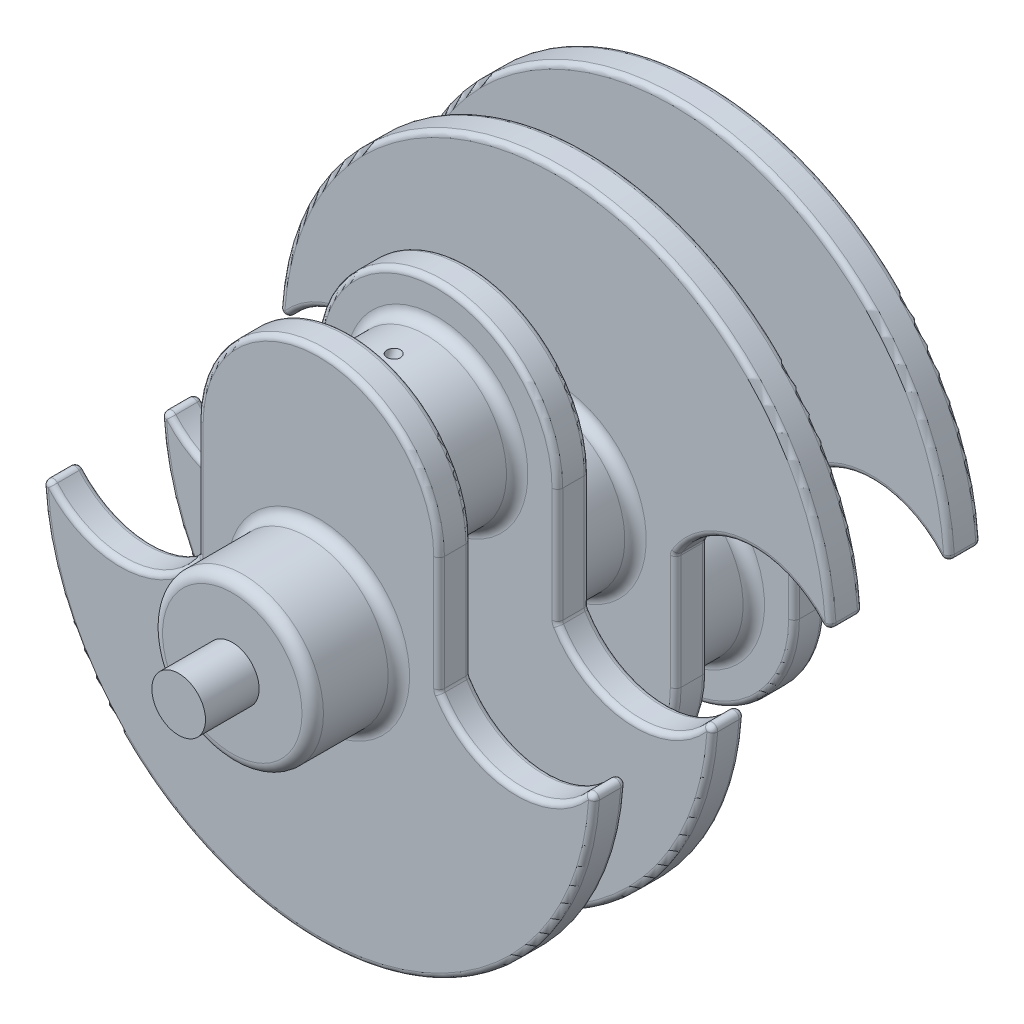
SolidWorks part; units mm, degrees
material "AISI 4340 Steel, normalized"
ref_plane "Front Plane" through (0, 0, 0) normal (0, 0, 1) x (1, 0, 0)
ref_plane "Top Plane" through (0, 0, 0) normal (0, 1, 0) x (1, 0, 0)
ref_plane "Right Plane" through (0, 0, 0) normal (1, 0, 0) x (0, 0, -1)
sketch "Sketch1" plane through (0, 0, 0) normal (0, 0, 1) x (1, 0, 0)
  circle A0 centre (0, 0) radius 30
  dimension "D1" = 30
extrude "Boss-Extrude1" add sketch "Sketch1" along normal blind 32.13
sketch "Sketch8" plane through (0, 0, 0) normal (0, 0, -1) x (-1, 0, 0)
  line L0 (-45, 43.2) -> (-45, 0)
  line L1 (45, 43.2) -> (45, 0)
  line L2 (-45, 0) -> (-89.1072, 0) construction
  arc A0 (45, 43.2) -> (-45, 43.2) centre (0, 43.2) ccw
  arc A5 (-103, 0) -> (103, 0) centre (0, 0) ccw
  arc A6 (-45, 0) -> (-103, 0) centre (-74, 16.8638) cw
  arc A7 (45, 0) -> (103, 0) centre (74, 16.8638) ccw
  dimension "D1" = 45
  dimension "D2" = 103
  dimension "D3" = 43.2
  dimension "D4" = 0
  dimension "D5" = 180
  dimension "D6" = 0
extrude "Boss-Extrude5" add sketch "Sketch8" along normal blind 12
sketch "Sketch2" plane through (0, 0, 32.13) normal (0, 0, 1) x (1, 0, 0)
  circle A0 centre (0, 0) radius 10
  dimension "D1" = 10
extrude "Boss-Extrude2" add sketch "Sketch2" along normal blind 20
sketch "Sketch9" plane through (0, 0, -12) normal (0, 0, -1) x (-1, 0, 0)
  circle A0 centre (0, 43.2) radius 30
  dimension "D2" = 30
  dimension "D1" = 43.2
extrude "Boss-Extrude6" add sketch "Sketch9" along normal blind 32.13
ref_plane "Plane4" through (0, 0, -88.26) normal (0, 0, -1) x (-1, 0, 0)
sketch "Sketch10" plane through (0, 0, -44.13) normal (0, 0, -1) x (-1, 0, 0)
  line L0 (-45, -43.2) -> (-45, 0)
  line L1 (45, -43.2) -> (45, 0)
  line L2 (45, 0) -> (85.967, 0) construction
  arc A0 (-45, -43.2) -> (45, -43.2) centre (0, -43.2) ccw
  arc A1 (-45, 0) -> (-103, 0) centre (-74, -16.8638) ccw
  arc A2 (45, 0) -> (103, 0) centre (74, -16.8638) cw
  arc A3 (-103, 0) -> (103, 0) centre (0, 0) cw
  dimension "D1" = 45
  dimension "D4" = 0
  dimension "D5" = 180
  dimension "D6" = 0
  dimension "D3" = 103
  dimension "D2" = 43.2
extrude "Boss-Extrude7" add sketch "Sketch10" along normal blind 12 from surface starting at plane "Plane4"
ref_plane "Plane3" through (0, 0, -132.39) normal (0, 0, -1) x (-1, 0, 0)
sketch "Sketch12" plane through (0, 0, -132.39) normal (0, 0, -1) x (-1, 0, 0)
  line L2 (45, -43.2) -> (45, 0)
  line L3 (45, -43.2) -> (45, 0)
  line L4 (-45, 0) -> (-45, -43.2)
  line L5 (-45, 0) -> (-45, -43.2)
  arc A12 (-45, -43.2) -> (45, -43.2) centre (0, -43.2) ccw
  arc A13 (103, 0) -> (45, 0) centre (74, -16.8638) ccw
  arc A14 (103, 0) -> (-103, 0) centre (0, 0) ccw
  arc A15 (-45, 0) -> (-103, 0) centre (-74, -16.8638) ccw
  arc A16 (-45, -43.2) -> (45, -43.2) centre (0, -43.2) ccw
  arc A17 (103, 0) -> (45, 0) centre (74, -16.8638) ccw
  arc A18 (103, 0) -> (-103, 0) centre (0, 0) ccw
  arc A19 (-45, 0) -> (-103, 0) centre (-74, -16.8638) ccw
  dimension "D1" = 0
extrude "Boss-Extrude8" add sketch "Sketch12" along normal blind 12
sketch "Sketch14" plane through (0, 0, -100.26) normal (0, 0, -1) x (-1, 0, 0)
  circle A0 centre (0, -43.2) radius 30
  dimension "D2" = 30
  dimension "D1" = 43.2
extrude "Boss-Extrude9" add sketch "Sketch14" along normal up to next
sketch "Sketch15" plane through (0, 0, -144.39) normal (0, 0, -1) x (-1, 0, 0)
  circle A1 centre (0, 0) radius 30
  circle A2 centre (0, 0) radius 30
  dimension "D1" = 0
extrude "Boss-Extrude10" add sketch "Sketch15" along normal blind 32.13
sketch "Sketch16" plane through (0, 0, -176.52) normal (0, 0, -1) x (-1, 0, 0)
  circle A1 centre (0, 0) radius 10
  circle A2 centre (0, 0) radius 10
  dimension "D1" = 0
extrude "Boss-Extrude11" add sketch "Sketch16" along normal blind 20
sketch "Sketch18" plane through (0, 0, -44.13) normal (0, 0, -1) x (-1, 0, 0)
  line L2 (-45, 43.2) -> (-45, 0)
  line L3 (-45, 43.2) -> (-45, 0)
  line L4 (45, 0) -> (45, 43.2)
  line L5 (45, 0) -> (45, 43.2)
  arc A4 (45, 43.2) -> (-45, 43.2) centre (0, 43.2) ccw
  arc A5 (-103, 0) -> (-45, 0) centre (-74, 16.8638) ccw
  arc A6 (-103, 0) -> (103, 0) centre (0, 0) ccw
  arc A7 (45, 0) -> (103, 0) centre (74, 16.8638) ccw
  arc A8 (45, 43.2) -> (-45, 43.2) centre (0, 43.2) ccw
  arc A9 (-103, 0) -> (-45, 0) centre (-74, 16.8638) ccw
  arc A10 (-103, 0) -> (103, 0) centre (0, 0) ccw
  arc A11 (45, 0) -> (103, 0) centre (74, 16.8638) ccw
  dimension "D1" = 0
extrude "Boss-Extrude12" add sketch "Sketch18" along normal blind 12
sketch "Sketch19" plane through (0, 0, -56.13) normal (0, 0, -1) x (-1, 0, 0)
  circle A1 centre (0, 0) radius 30
  circle A2 centre (0, 0) radius 30
  dimension "D1" = 0
extrude "Boss-Extrude13" add sketch "Sketch19" along normal up to next
fillet "Fillet1" radius 2 32 edges at (0, -103, -44.13) (-74, -16.683, -44.13) (-45, 21.6, -44.13) (45, 21.6, -44.13) (74, -16.683, -44.13) (0, -103, -56.13) (-74, -16.683, -56.13) (-45, 21.6, -56.13) (0, 88.2, -56.13) (45, 21.6, -56.13) (74, -16.683, -56.13) (103, 0, -50.13) (45, 0, -50.13) (-45, 0, -50.13) (-103, 0, -50.13) (0, 88.2, -44.13) (45, 21.6, 0) (74, -16.683, 0) (0, -103, 0) (-74, -16.683, 0) (-45, 21.6, 0) (0, 88.2, -12) (45, 21.6, -12) (74, -16.683, -12) (0, -103, -12) (-74, -16.683, -12) (-45, 21.6, -12) (-45, 0, -6) (-103, 0, -6) (103, 0, -6) (45, 0, -6) (0, 88.2, 0)
fillet "Fillet2" radius 2 16 edges at (0, 103, -132.39) (74, 16.683, -132.39) (45, -21.6, -132.39) (0, -88.2, -132.39) (-45, -21.6, -132.39) (-74, 16.683, -132.39) (74, 16.683, -144.39) (45, -21.6, -144.39) (0, -88.2, -144.39) (-45, -21.6, -144.39) (-74, 16.683, -144.39) (-103, 0, -138.39) (-45, 0, -138.39) (45, 0, -138.39) (103, 0, -138.39) (0, 103, -144.39)
fillet "Fillet3" radius 2 16 edges at (45, -21.6, -88.26) (74, 16.683, -88.26) (0, 103, -88.26) (-74, 16.683, -88.26) (-45, -21.6, -88.26) (0, -88.2, -88.26) (45, -21.6, -100.26) (74, 16.683, -100.26) (-74, 16.683, -100.26) (-45, -21.6, -100.26) (0, -88.2, -100.26) (45, 0, -94.26) (103, 0, -94.26) (-103, 0, -94.26) (-45, 0, -94.26) (0, 103, -100.26)
fillet "Fillet5" radius 4 2 edges at (30, 0, 32.13) (30, 0, 0)
fillet "Fillet6" radius 4 2 edges at (-30, 0, -144.39) (-30, 0, -176.52)
ref_plane "Plane5" through (0, 31.75, 0) normal (0, 1, 0) x (1, 0, 0)
sketch "Sketch20" plane through (0, 0, 0) normal (1, 0, 0) x (0, 0, -1)
  line L1 (100.26, -73.2) -> (100.26, -13.2)
  line L2 (100.26, -73.2) -> (100.26, -13.2)
  dimension "D1" = 0
ref_plane "Plane6" through (0, -73.2, 0) normal (0, 1, 0) x (1, 0, 0)
sketch "Sketch21" plane through (0, 31.75, 0) normal (0, 1, 0) x (1, 0, 0)
  line L2 (-30, 172.52) -> (30, 172.52) construction
  line L3 (-30, 172.52) -> (-30, 148.39) construction
  line L4 (-30, 148.39) -> (30, 148.39) construction
  line L5 (30, 172.52) -> (30, 148.39) construction
  circle A0 centre (0, 160.455) radius 2.5
  point P10 (0, 172.52)
  point P11 (30, 160.455)
  dimension "D1" = 5
sketch "Sketch27" plane through (0, 0, 0) normal (0, 0, 1) x (1, 0, 0)
  line L0 (0, 73.2) -> (0, -30) construction
  circle A1 centre (0, 43.2) radius 30
  circle A2 centre (0, 43.2) radius 30 construction
  circle A3 centre (0, 0) radius 30
  circle A4 centre (0, 0) radius 30 construction
  dimension "D1" = 0
  dimension "D2" = 0
ref_plane "Plane8" through (0, 73.2, 0) normal (0, -1, 0) x (-1, 0, 0)
ref_plane "Plane9" through (0, -30, 0) normal (0, -1, 0) x (-1, 0, 0)
sketch "Sketch28" plane through (0, -30, 0) normal (0, -1, 0) x (-1, 0, 0)
  line L1 (-30, -4) -> (30, -4) construction
  line L2 (-30, -4) -> (-30, -28.13) construction
  line L3 (-30, -28.13) -> (30, -28.13) construction
  line L4 (30, -4) -> (30, -28.13) construction
  line L5 (-30, -4) -> (30, -28.13) construction
  line L6 (-30, -28.13) -> (30, -4) construction
  circle A0 centre (0, -16.065) radius 2.5
  point P4 (0, -16.065)
  dimension "D1" = 5
sketch "Sketch29" plane through (0, 73.2, 0) normal (0, -1, 0) x (-1, 0, 0)
  line L1 (30, 44.13) -> (-30, 44.13) construction
  line L2 (30, 44.13) -> (30, 12) construction
  line L3 (30, 12) -> (-30, 12) construction
  line L4 (-30, 44.13) -> (-30, 12) construction
  line L5 (30, 44.13) -> (-30, 12) construction
  line L6 (30, 12) -> (-30, 44.13) construction
  circle A0 centre (0, 28.065) radius 2.5
  point P4 (0, 28.065)
sketch "Sketch31" plane through (0, 0, 0) normal (1, 0, 0) x (0, 0, -1)
  line L0 (28.065, 73.2) -> (-16.065, -30) construction
ref_plane "Plane10" through (0, 73.2, -28.065) normal (0, -0.9195, 0.3932) x (-1, 0, 0)
ref_plane "Plane11" through (0, -30, 16.065) normal (0, -0.9195, 0.3932) x (-1, 0, 0)
combine bodies "Combine1" operation type add bodies to combine 119 109 117
fillet "Fillet7" radius 4 6 edges at (-30, 43.2, -44.13) (-30, 43.2, -12) (-30, 0, -56.13) (-30, 0, -88.26) (-30, -43.2, -132.39) (-30, -43.2, -100.26)
sketch "Sketch39" plane through (0, -73.2, 0) normal (0, 1, 0) x (1, 0, 0)
  line L1 (30, 128.39) -> (-30, 128.39) construction
  line L2 (30, 128.39) -> (30, 104.26) construction
  line L3 (30, 104.26) -> (-30, 104.26) construction
  line L4 (-30, 128.39) -> (-30, 104.26) construction
  line L5 (30, 128.39) -> (-30, 104.26) construction
  line L6 (30, 104.26) -> (-30, 128.39) construction
  point P4 (0, 116.325)
sketch "Sketch40" plane through (0, 0, 0) normal (1, 0, 0) x (0, 0, -1)
  line L0 (160.455, 31.75) -> (116.325, -73.2) construction
  line L1 (172.52, 31.75) -> (148.39, 31.75) construction
ref_plane "Plane12" through (0, 31.75, -160.455) normal (0, -0.9218, 0.3876) x (-1, 0, 0)
ref_plane "Plane13" through (0, -73.2, -116.325) normal (0, -0.9218, 0.3876) x (-1, 0, 0)
sketch "Sketch47" plane through (0, 73.2, -28.065) normal (0, -0.9195, 0.3932) x (-1, 0, 0)
  ellipse E0 centre (0, 0) end of major axis (2.5, 0) minor radius 2.2987 construction
  ellipse E1 centre (0, 0) end of major axis (2.5, 0) minor radius 2.2987
extrude "Cut-Extrude1" cut sketch "Sketch47" along normal through all
sketch "Sketch48" plane through (0, -30, 16.065) normal (0, -0.9195, 0.3932) x (-1, 0, 0)
  ellipse E0 centre (0, 0) end of major axis (2.5, 0) minor radius 2.2987 construction
  ellipse E1 centre (0, 0) end of major axis (2.5, 0) minor radius 2.2987
extrude "Cut-Extrude2" cut sketch "Sketch48" against normal through all
sketch "Sketch49" plane through (0, -73.2, -116.325) normal (0, -0.9218, 0.3876) x (-1, 0, 0)
  circle A0 centre (0, 0) radius 2.5
  dimension "D1" = 5
extrude "Cut-Extrude3" cut sketch "Sketch49" against normal through all
sketch "Sketch50" plane through (0, 31.75, -160.455) normal (0, -0.9218, 0.3876) x (-1, 0, 0)
  circle A0 centre (0, 0) radius 2.5 construction
  circle A1 centre (0, 0) radius 2.5
extrude "Cut-Extrude4" cut sketch "Sketch50" along normal through all
equation "\"CRR\"= 43.2mm'Crank Radius"
equation "\"D1@Sketch9\"=\"CRR\""
equation "\"D1@Sketch14\"=\"CRR\""
equation "\"JR\"= 30mm'Journal Radius"
equation "\"D1@Sketch1\"=\"JR\""
equation "\"D2@Sketch9\"=\"JR\""
equation "\"D2@Sketch14\"=\"JR\""
equation "\"LT\"= 12mm'Lobe Thickness"
equation "\"D1@Boss-Extrude5\"=\"LT\""
equation "\"D1@Boss-Extrude7\"=\"LT\""
equation "\"D1@Boss-Extrude8\"=\"LT\""
equation "\"D1@Boss-Extrude12\"=\"LT\""
equation "\"D3@Sketch8\"=\"CRR\""
equation "\"D2@Sketch10\"=\"CRR\""
equation "\"JL\"= 24.13 + 2 * ( \"JF\" )'Journal Length"
equation "\"D1@Boss-Extrude1\"=\"JL\""
equation "\"D1@Boss-Extrude6\"=\"JL\""
equation "\"D1@Boss-Extrude10\"=\"JL\""
equation "\"LHD\"= 5mm'Lubrication Hole Diameter"
equation "\"D1@Sketch29\"=\"LHD\""
equation "\"JF\"= 4mm'Internal Journal Fillets"
equation "\"D1@Fillet7\"=\"JF\""
equation "\"D1@Fillet6\"=\"JF\""
equation "\"LR\"= 45mm'Lobe radius"
equation "\"CWR\"= 103mm'Counterweight Radius"
equation "\"D1@Sketch8\"=\"LR\""
equation "\"D2@Sketch8\"=\"CWR\""
equation "\"D3@Sketch10\"=\"CWR\""
equation "\"D1@Sketch10\"=\"LR\""
equation "\"CWA\"= 3.14159rad'Counterweight Arc"
equation "\"CWS\"= 0rad'Counterweight Slope"
equation "\"CWH\"= 0mm'Counterweight Offset"
equation "\"D4@Sketch8\"=\"CWH\""
equation "\"D5@Sketch8\"=\"CWA\""
equation "\"D6@Sketch8\"=\"CWS\""
equation "\"D4@Sketch10\"=\"CWH\""
equation "\"D5@Sketch10\"=\"CWA\""
equation "\"D6@Sketch10\"=\"CWS\""
